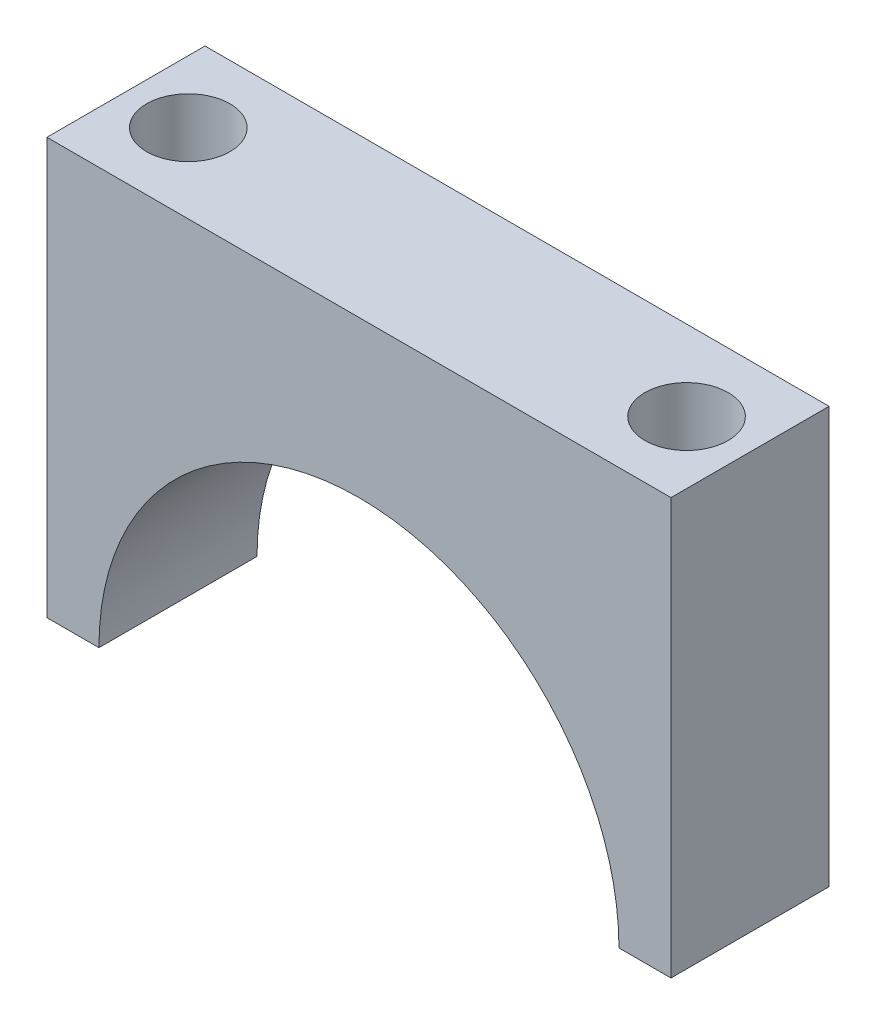
SolidWorks part; units mm, degrees
ref_plane "Front Plane" through (0, 0, 0) normal (0, 0, 1) x (1, 0, 0)
ref_plane "Top Plane" through (0, 0, 0) normal (0, 1, 0) x (1, 0, 0)
ref_plane "Right Plane" through (0, 0, 0) normal (1, 0, 0) x (0, 0, -1)
sketch "Sketch1" plane through (0, 0, 0) normal (0, 0, 1) x (1, 0, 0)
  line L3 (2492.4858, 1406.0405) -> (2492.4858, 1431.4405)
  line L4 (2492.4858, 1431.4405) -> (2530.5858, 1431.4405)
  line L5 (2530.5858, 1431.4405) -> (2530.5858, 1406.0405)
  line L8 (2492.4858, 1406.0405) -> (2495.6608, 1406.0405)
  line L9 (2530.5858, 1406.0405) -> (2527.4108, 1406.0405)
  line L10 (2495.6608, 1406.0405) -> (2527.4108, 1406.0405)
  dimension "D1" = 3.175
  dimension "D2" = 38.1
  dimension "D3" = 3.175
  dimension "D4" = 25.4
extrude "Boss-Extrude1" add sketch "Sketch1" along normal blind 9.652
sketch "Sketch2" plane through (0, 1431.4405, 0) normal (0, 1, 0) x (1, 0, 0)
  line L0 (2492.4858, 0) -> (2492.4858, -9.652) construction
  line L1 (2530.5858, -9.652) -> (2492.4858, -9.652) construction
  line L2 (2492.4858, -9.652) -> (2492.4858, 0) construction
  line L3 (2511.5358, 5.2296) -> (2511.5358, -16.0947) construction
  circle A0 centre (2496.2958, -4.8311) radius 2.54
  circle A1 centre (2526.7758, -4.8923) radius 2.54
  dimension "D1" = 15.24
  dimension "D2" = 15.24
extrude "Cut-Extrude1" cut sketch "Sketch2" against normal blind 5.08
sketch "Sketch3" plane through (0, 0, 9.652) normal (0, 0, 1) x (1, 0, 0)
  line L0 (2492.4858, 1406.0405) -> (2530.5858, 1406.0405) construction
  circle A0 centre (2511.5358, 1406.0405) radius 15.875
extrude "Cut-Extrude2" cut sketch "Sketch3" against normal blind 50.038
